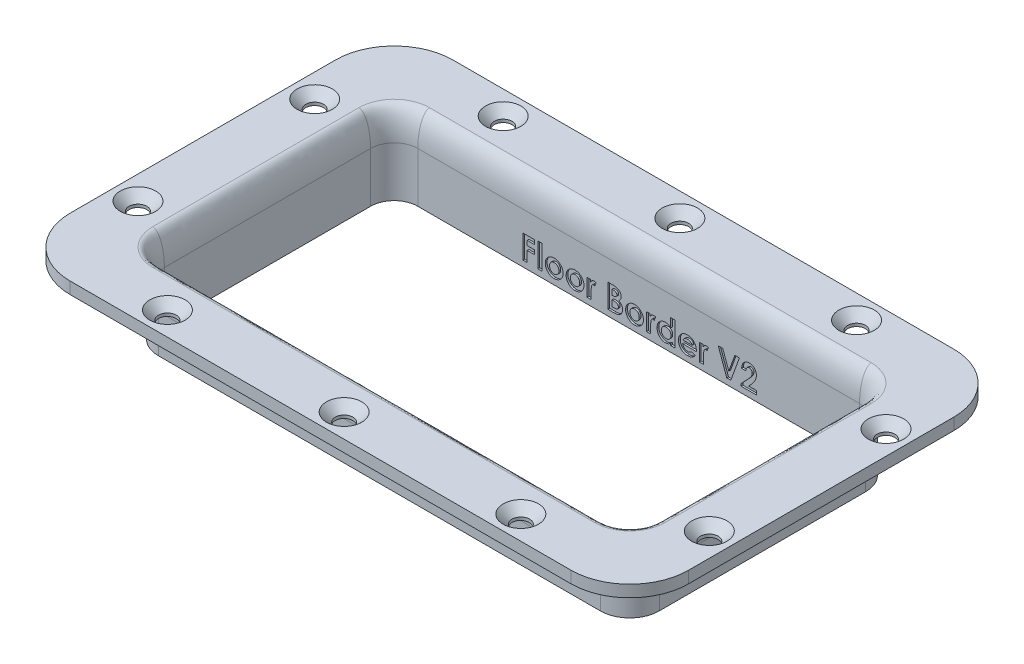
SolidWorks part; units mm, degrees
ref_plane "Front Plane" through (0, 0, 0) normal (0, 0, 1) x (1, 0, 0)
ref_plane "Top Plane" through (0, 0, 0) normal (0, 1, 0) x (1, 0, 0)
ref_plane "Right Plane" through (0, 0, 0) normal (1, 0, 0) x (0, 0, -1)
sketch "Sketch1" plane through (0, 0, 0) normal (0, 1, 0) x (1, 0, 0)
  line L0 (-52.705, 22.225) -> (-52.705, -22.225)
  line L1 (-47.625, 28.575) -> (47.625, 28.575)
  line L2 (-53.975, 22.225) -> (-53.975, -22.225)
  line L3 (-47.625, -28.575) -> (47.625, -28.575)
  line L4 (53.975, 22.225) -> (53.975, -22.225)
  line L5 (-53.975, 28.575) -> (53.975, -28.575) construction
  line L6 (-53.975, -28.575) -> (53.975, 28.575) construction
  line L7 (-47.625, -27.305) -> (47.625, -27.305)
  line L8 (52.705, 22.225) -> (52.705, -22.225)
  line L9 (-47.625, 27.305) -> (47.625, 27.305)
  arc A0 (47.625, 28.575) -> (53.975, 22.225) centre (47.625, 22.225) cw
  arc A1 (47.625, -28.575) -> (53.975, -22.225) centre (47.625, -22.225) ccw
  arc A2 (-53.975, -22.225) -> (-47.625, -28.575) centre (-47.625, -22.225) ccw
  arc A3 (-47.625, 28.575) -> (-53.975, 22.225) centre (-47.625, 22.225) ccw
  arc A4 (-52.705, -22.225) -> (-47.625, -27.305) centre (-47.625, -22.225) ccw
  arc A5 (47.625, -27.305) -> (52.705, -22.225) centre (47.625, -22.225) ccw
  arc A6 (47.625, 27.305) -> (52.705, 22.225) centre (47.625, 22.225) cw
  arc A7 (-47.625, 27.305) -> (-52.705, 22.225) centre (-47.625, 22.225) ccw
  point P0 (0, 0)
  dimension "D1" = 6.35
  dimension "D2" = 107.95
  dimension "D3" = 57.15
  dimension "D4" = 1.27
extrude "Boss-Extrude1" add sketch "Sketch1" along normal blind 14.605
sketch "Sketch2" plane through (0, 14.605, 0) normal (0, 1, 0) x (1, 0, 0)
  line L0 (47.625, 28.575) -> (-47.625, 28.575) construction
  line L1 (-53.975, -41.275) -> (53.975, -41.275)
  line L2 (-66.675, -28.575) -> (-66.675, 28.575)
  line L3 (-53.975, 41.275) -> (53.975, 41.275)
  line L4 (66.675, -28.575) -> (66.675, 28.575)
  line L5 (-66.675, -41.275) -> (66.675, 41.275) construction
  line L6 (-66.675, 41.275) -> (66.675, -41.275) construction
  line L7 (-53.975, 22.225) -> (-53.975, -22.225) construction
  line L16 (52.705, -22.225) -> (52.705, 22.225)
  line L17 (-47.625, -27.305) -> (47.625, -27.305)
  line L18 (-52.705, 22.225) -> (-52.705, -22.225)
  line L19 (47.625, 27.305) -> (-47.625, 27.305)
  line L20 (52.705, -22.225) -> (52.705, 22.225)
  line L21 (-47.625, -27.305) -> (47.625, -27.305)
  line L22 (-52.705, 22.225) -> (-52.705, -22.225)
  line L23 (47.625, 27.305) -> (-47.625, 27.305)
  arc A0 (53.975, 41.275) -> (66.675, 28.575) centre (53.975, 28.575) cw
  arc A1 (53.975, -41.275) -> (66.675, -28.575) centre (53.975, -28.575) ccw
  arc A2 (-53.975, -41.275) -> (-66.675, -28.575) centre (-53.975, -28.575) cw
  arc A3 (-66.675, 28.575) -> (-53.975, 41.275) centre (-53.975, 28.575) cw
  arc A12 (52.705, 22.225) -> (47.625, 27.305) centre (47.625, 22.225) ccw
  arc A13 (47.625, -27.305) -> (52.705, -22.225) centre (47.625, -22.225) ccw
  arc A14 (-52.705, -22.225) -> (-47.625, -27.305) centre (-47.625, -22.225) ccw
  arc A15 (-47.625, 27.305) -> (-52.705, 22.225) centre (-47.625, 22.225) ccw
  arc A16 (52.705, 22.225) -> (47.625, 27.305) centre (47.625, 22.225) ccw
  arc A17 (47.625, -27.305) -> (52.705, -22.225) centre (47.625, -22.225) ccw
  arc A18 (-52.705, -22.225) -> (-47.625, -27.305) centre (-47.625, -22.225) ccw
  arc A19 (-47.625, 27.305) -> (-52.705, 22.225) centre (-47.625, 22.225) ccw
  point P0 (0, 0)
  dimension "D3" = 12.7
  dimension "D1" = 12.7
  dimension "D2" = 12.7
  dimension "D4" = 1.27
extrude "Boss-Extrude2" add sketch "Sketch2" along normal blind 2.54
fillet "Fillet1" radius 6.35 8 edges at (-52.1151, 14.605, -26.7151) (0, 14.605, -28.575) (52.1151, 14.605, -26.7151) (53.975, 14.605, 0) (52.1151, 14.605, 26.7151) (0, 14.605, 28.575) (-52.1151, 14.605, 26.7151) (-53.975, 14.605, 0)
fillet "Fillet3" radius 2.54 8 edges at (51.2171, 17.145, -25.8171) (52.705, 17.145, 0) (51.2171, 17.145, 25.8171) (0, 17.145, 27.305) (-51.2171, 17.145, 25.8171) (-52.705, 17.145, 0) (-51.2171, 17.145, -25.8171) (0, 17.145, -27.305) second distance 6.35 first distance on face at (0, 17.145, 0)
sketch "Sketch3" plane through (0, 17.145, 0) normal (0, 1, 0) x (1, 0, 0)
  line L4 (-9.4367, 0) -> (9.4367, 0) construction
  line L5 (0, -9.4367) -> (0, 9.4367) construction
  line L8 (53.975, 36.195) -> (-53.975, 36.195)
  line L9 (-61.595, 28.575) -> (-61.595, -28.575)
  line L10 (-53.975, -36.195) -> (53.975, -36.195)
  line L11 (61.595, -28.575) -> (61.595, 28.575)
  line L12 (53.975, 36.195) -> (-53.975, 36.195)
  line L13 (-61.595, 28.575) -> (-61.595, -28.575)
  line L14 (-53.975, -36.195) -> (53.975, -36.195)
  line L15 (61.595, -28.575) -> (61.595, 28.575)
  circle A4 centre (-61.595, -19.05) radius 1.905
  circle A5 centre (-38.1, -36.195) radius 1.905
  circle A6 centre (-38.1, 36.195) radius 1.905
  circle A7 centre (61.595, -19.05) radius 1.905
  arc A8 (61.595, 28.575) -> (53.975, 36.195) centre (53.975, 28.575) ccw
  arc A9 (-53.975, 36.195) -> (-61.595, 28.575) centre (-53.975, 28.575) ccw
  arc A10 (-61.595, -28.575) -> (-53.975, -36.195) centre (-53.975, -28.575) ccw
  arc A11 (53.975, -36.195) -> (61.595, -28.575) centre (53.975, -28.575) ccw
  arc A12 (61.595, 28.575) -> (53.975, 36.195) centre (53.975, 28.575) ccw
  arc A13 (-53.975, 36.195) -> (-61.595, 28.575) centre (-53.975, 28.575) ccw
  arc A14 (-61.595, -28.575) -> (-53.975, -36.195) centre (-53.975, -28.575) ccw
  arc A15 (53.975, -36.195) -> (61.595, -28.575) centre (53.975, -28.575) ccw
  circle A16 centre (0, -36.195) radius 1.905
  circle A17 centre (38.1, 36.195) radius 1.905
  circle A18 centre (38.1, -36.195) radius 1.905
  circle A19 centre (61.595, 19.05) radius 1.905
  circle A20 centre (0, 36.195) radius 1.905
  circle A21 centre (-61.595, 19.05) radius 1.905
  dimension "D2" = 3.81
  dimension "D3" = 38.1
  dimension "D4" = 38.1
  dimension "D1" = 5.08
extrude "Cut-Extrude1" cut sketch "Sketch3" against normal through all contours A16 | A5 | A4 | A21 | A6 | A20 | A17 | A19 | A7 | A18
chamfer "Chamfer1" distance 1.905 angle 45 10 edges at (-38.1, 17.145, 38.1) (0, 17.145, 38.1) (38.1, 17.145, 34.29) (61.595, 17.145, 17.145) (61.595, 17.145, -17.145) (38.1, 17.145, -34.29) (0, 17.145, -38.1) (-38.1, 17.145, -38.1) (-61.595, 17.145, -20.955) (-61.595, 17.145, 20.955)
sketch "Sketch4" plane through (0, 0, -27.305) normal (0, 0, 1) x (1, 0, 0)
  line L0 (-39.3063, 1.27) -> (39.3063, 1.27) construction
  line L1 (47.625, 0) -> (-47.625, 0) construction
  text T0 "<b>Floor Border V2</b>" font "Century Gothic" height 5.08
  point P2 (0, 1.27)
  point P3 (0, 0)
  point P4 (0, 0)
  dimension "D1" = 1.27
extrude "Cut-Extrude2" cut sketch "Sketch4" against normal blind 0.381
